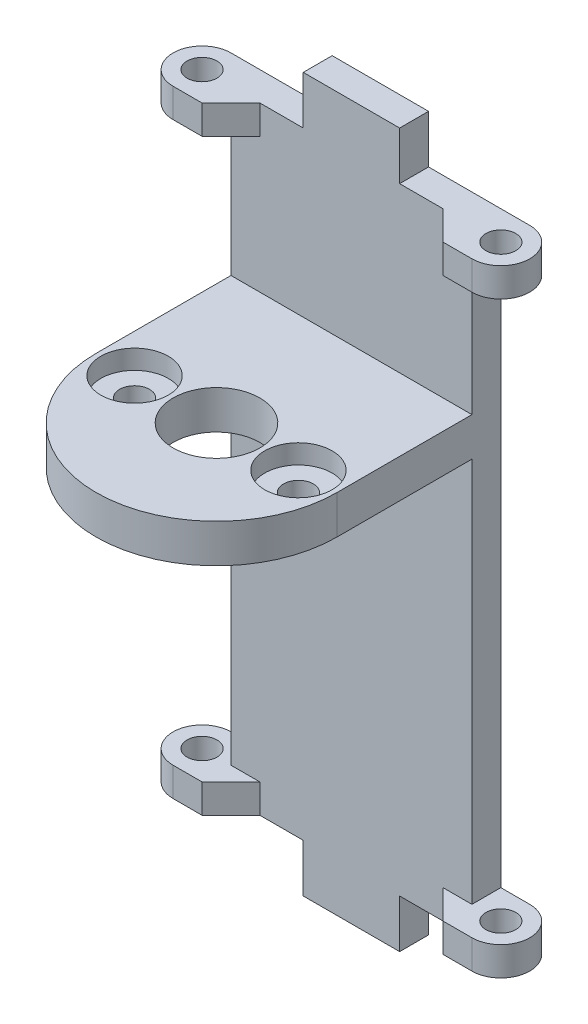
SolidWorks part; units mm, degrees
ref_plane "Front Plane" through (0, 0, 0) normal (0, 0, 1) x (1, 0, 0)
ref_plane "Top Plane" through (0, 0, 0) normal (0, 1, 0) x (1, 0, 0)
ref_plane "Right Plane" through (0, 0, 0) normal (1, 0, 0) x (0, 0, -1)
sketch "Sketch11" plane through (0, 0, 51.65) normal (0, -1, 0) x (1, 0, 0)
  line L0 (12.5, 85.5) -> (12.5, 71.5)
  line L1 (-12.5, 85.5) -> (-12.5, 71.5)
  line L3 (0, 71.5) -> (0, 85.5) construction
  line L6 (-12.5, 71.5) -> (12.5, 71.5)
  line L7 (-8.5, 85.5) -> (8.5, 85.5) construction
  circle A0 centre (-8.5, 85.5) radius 1.55
  circle A1 centre (8.5, 85.5) radius 1.55
  circle A4 centre (0, 85.5) radius 4.5
  arc A5 (-12.5, 85.5) -> (12.5, 85.5) centre (0, 85.5) cw
  point P15 (0, 85.5)
extrude "Boss-Extrude1" add sketch "Sketch11" along normal blind 4
sketch "Sketch12" plane through (0, 0, 123.15) normal (0, 0, -1) x (-1, 0, 0)
  line L0 (-12.5, 0) -> (-12.5, 17)
  line L1 (12.5, 0) -> (12.5, 17)
  line L3 (-12.5, 0) -> (-12.5, -4)
  line L4 (-12.5, -4) -> (-12.5, -47)
  line L5 (12.5, 0) -> (12.5, -4)
  line L6 (12.5, -4) -> (12.5, -47)
  line L8 (-12.5, 17) -> (-5, 17)
  line L9 (-5, 17) -> (-5, 22)
  line L12 (5, 17) -> (12.5, 17)
  line L13 (-5, 22) -> (5, 22)
  line L14 (5, 22) -> (5, 17)
  line L15 (-12.5, -47) -> (-5, -47)
  line L16 (-5, -47) -> (-5, -52)
  line L17 (-5, -52) -> (5, -52)
  line L18 (5, -52) -> (5, -47)
  line L19 (5, -47) -> (12.5, -47)
extrude "Boss-Extrude2" add sketch "Sketch12" along normal blind 3
sketch "Sketch13" plane through (0, 0, 0) normal (0, 1, 0) x (1, 0, 0)
  circle A0 centre (-8.5, -137.15) radius 3.5
  circle A1 centre (8.5, -137.15) radius 3.5
extrude "Cut-Extrude1" cut sketch "Sketch13" against normal blind 2
ref_plane "Plane1" through (0, 17, 0) normal (0, 1, 0) x (1, 0, 0)
sketch "Sketch14" plane through (0, 17, 0) normal (0, 1, 0) x (1, 0, 0)
  line L0 (12.5, -123.15) -> (15.5, -123.15) construction
  line L1 (-12.5, -137.15) -> (-12.5, -123.15) construction
  line L2 (-12.5, -123.15) -> (-15.5, -123.15) construction
  line L3 (5, -123.15) -> (12.5, -123.15) construction
  line L4 (12.5, -123.15) -> (12.5, -137.15) construction
  line L6 (15.5, -120.15) -> (-15.5, -120.15)
  line L7 (-15.5, -126.15) -> (-12.5, -126.15)
  line L11 (12.5, -126.15) -> (15.5, -126.15)
  line L12 (-12.5, -126.15) -> (-9.5, -123.15)
  line L13 (12.5, -126.15) -> (9.5, -123.15)
  line L15 (-12.5, -123.15) -> (12.5, -123.15) construction
  line L16 (9.5, -123.15) -> (-9.5, -123.15)
  arc A0 (-15.5, -120.15) -> (-15.5, -126.15) centre (-15.5, -123.15) ccw
  circle A1 centre (-15.5, -123.15) radius 1.55
  circle A2 centre (15.5, -123.15) radius 1.55
  arc A3 (15.5, -120.15) -> (15.5, -126.15) centre (15.5, -123.15) cw
extrude "Boss-Extrude3" add sketch "Sketch14" against normal blind 3
ref_plane "Plane2" through (0, -47, 0) normal (0, -1, 0) x (-1, 0, 0)
sketch "Sketch15" plane through (0, -47, 0) normal (0, -1, 0) x (-1, 0, 0)
  line L0 (15.5, -126.15) -> (12.5, -126.15) construction
  line L1 (15.5, -120.15) -> (-15.5, -120.15)
  line L2 (-15.5, -126.15) -> (-12.5, -126.15)
  line L3 (-12.5, -126.15) -> (-9.5, -123.15)
  line L4 (-12.5, -123.15) -> (-5, -123.15) construction
  line L5 (15.5, -126.15) -> (12.5, -126.15)
  line L6 (12.5, -126.15) -> (9.5, -123.15)
  line L7 (5, -123.15) -> (12.5, -123.15) construction
  line L8 (9.5, -123.15) -> (-9.5, -123.15)
  circle A0 centre (15.5, -123.15) radius 1.55
  circle A1 centre (-15.5, -123.15) radius 1.55
  arc A2 (15.5, -120.15) -> (15.5, -126.15) centre (15.5, -123.15) cw
  arc A3 (-15.5, -120.15) -> (-15.5, -126.15) centre (-15.5, -123.15) ccw
  arc A4 (-15.5, -120.15) -> (-15.5, -126.15) centre (-15.5, -123.15) ccw construction
extrude "Boss-Extrude4" add sketch "Sketch15" against normal blind 3
